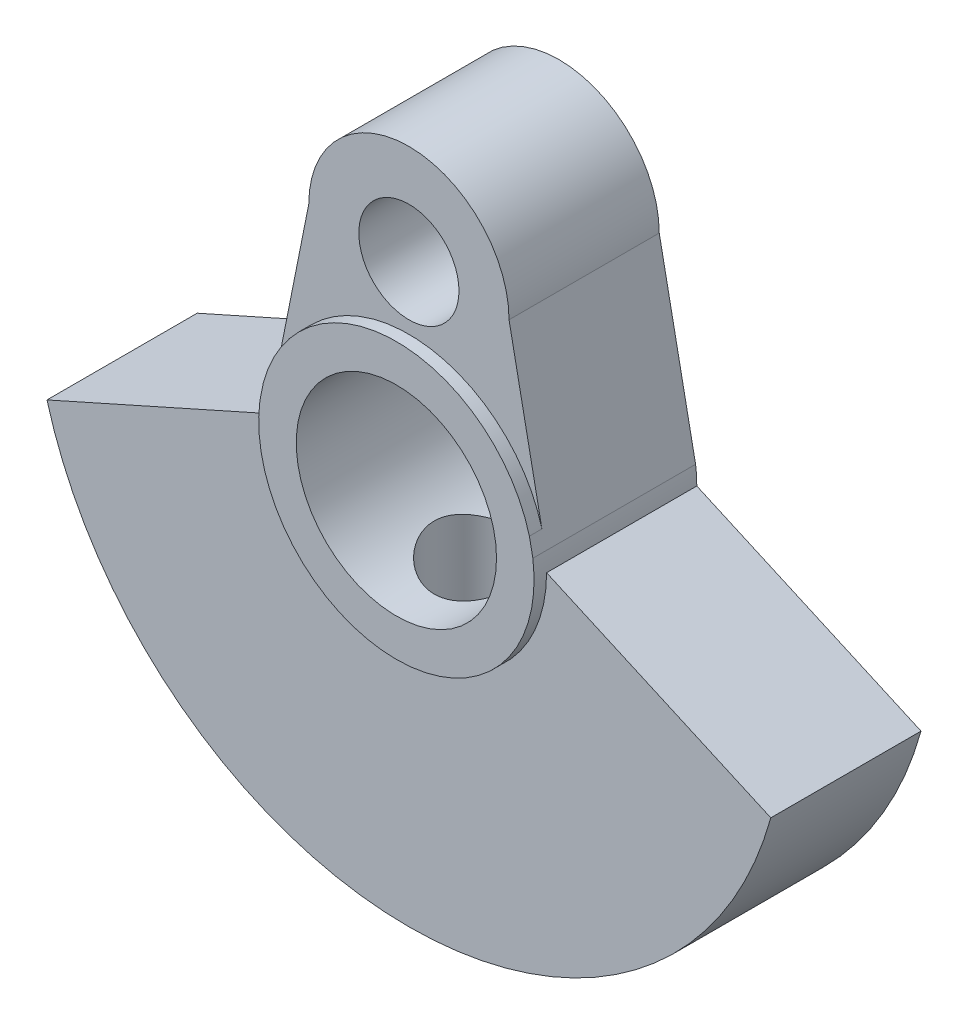
SolidWorks part; units mm, degrees
note: The reader was unsure of these and kept them because the rebuilt part matched: shared geometry of "Sketch1<5>".
ref_plane "Front Plane" through (0, 0, 0) normal (0, 0, 1) x (1, 0, 0)
ref_plane "Top Plane" through (0, 0, 0) normal (0, 1, 0) x (1, 0, 0)
ref_plane "Right Plane" through (0, 0, 0) normal (1, 0, 0) x (0, 0, -1)
sketch "Sketch1" plane through (0, 0, 0) normal (0, 0, 1) x (1, 0, 0)
  line L0 (-14.4568, -4) -> (-5.5, 0)
  line L1 (14.4568, -4) -> (5.5, 0)
  line L2 (-4, 8) -> (-5.4518, 0.7269)
  line L3 (0, -11.1478) -> (0, 18.1497) construction
  line L4 (4, 8) -> (5.4518, 0.7269)
  circle A0 centre (0, 0) radius 5.5
  circle A1 centre (0, 8) radius 2
  arc A2 (4, 8) -> (-4, 8) centre (0, 8) ccw
  arc A3 (-14.4568, -4) -> (14.4568, -4) centre (0, 0) ccw
  circle A4 centre (0, 0) radius 4
  dimension "D1" = 4
  dimension "D2" = 8
  dimension "D3" = 11
  dimension "D4" = 15
  dimension "D7" = 8
  dimension "D5" = 4
  dimension "D6" = 8
extrude "Boss-Extrude1" add sketch "Sketch1" along normal mid plane 6
extrude "Boss-Extrude4" add sketch "Sketch1<5>" along normal blind 6.5 from surface at -3 contours L3 A0 L4 A4 | A0 L3 A4 L2 starting at face at (0, -6.125, -3)
sketch "Sketch1<5>" plane through (0, 0, 0) normal (0, 0, 1) x (1, 0, 0) same geometry as "Sketch1"
ref_plane "Plane1" through (0, -15, 0) normal (0, 1, 0) x (1, 0, 0)
hole_wizard "Ø4.0 (4) Diameter Hole1" positions "3DSketch1" profile "Sketch4" hole size "Ø4.0" standard "DIN"
sketch3d "3DSketch1"
  point P0 (0, 0, 0)
  point P3 (0, 0, 0)
  point P5 (0, 0, 0)
  point P7 (0, 0, 0)
  point P9 (0, 0, 0)
  point P12 (0, 0, 0)
  point P18 (0, -15, -0.0161)
sketch "Sketch4" plane through (0, -15, -0.0161) normal (1, 0, 0) x (0, 0, -1)
  line L0 (0, 0) -> (0, 15)
  line L1 (0, 15) -> (2, 15)
  line L2 (2, 15) -> (2, 0)
  line L5 (2, 0) -> (0, 0)
  line L11 (0, -6.35) -> (0, 107.95) construction
  dimension "Thru Hole Dia." = 4
  dimension "Thru Hole Depth" = 15
